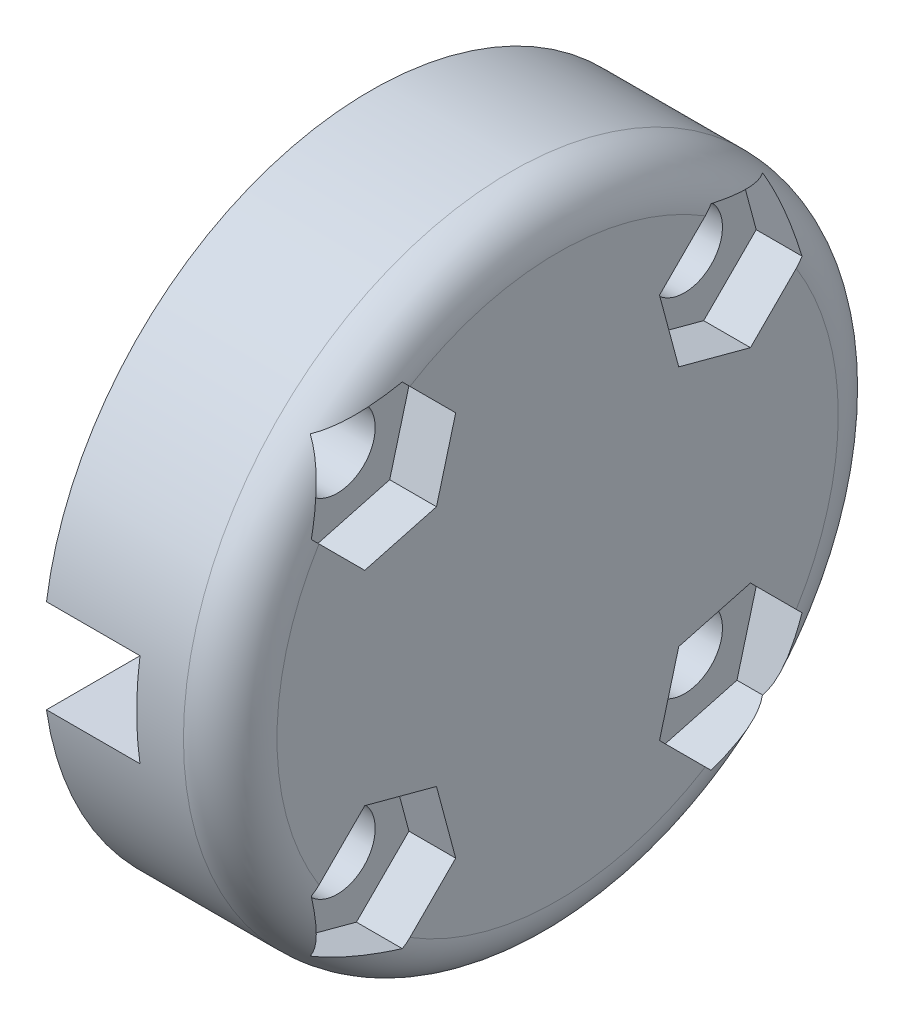
SolidWorks part; units mm, degrees
ref_plane "Front Plane" through (0, 0, 0) normal (0, 0, 1) x (1, 0, 0)
ref_plane "Top Plane" through (0, 0, 0) normal (0, 1, 0) x (1, 0, 0)
ref_plane "Right Plane" through (0, 0, 0) normal (1, 0, 0) x (0, 0, -1)
ref_plane "Plane1" through (-5, 0, 0) normal (1, 0, 0) x (0, 0, -1)
sketch "Sketch2" plane through (0, 0, 0) normal (1, 0, 0) x (0, 0, -1)
  line L1 (0, -14.5054) -> (0, 14.5054) construction
  line L2 (32.66, 0) -> (-15.2452, 0) construction
  line L3 (-10.918, -10.918) -> (10.918, 10.918) construction
  line L4 (12.2462, -12.2462) -> (-12.2462, 12.2462) construction
  circle A1 centre (0, 0) radius 2.625 construction
  circle A2 centre (0, 0) radius 14 construction
  circle A3 centre (0, 0) radius 10.5 construction
  circle A5 centre (0, 0) radius 24 construction
  point P17 (0, 0)
  point P18 (0, 0)
  point P19 (0, 0)
  dimension "D1" = 28
  dimension "D3" = 5.25
  dimension "D6" = 21
  dimension "D8" = 48
  dimension "D4" = 45
  dimension "D5" = 45
sketch "Sketch4" plane through (0, 0, 0) normal (1, 0, 0) x (0, 0, -1)
  line L0 (-10.918, -10.918) -> (10.918, 10.918) construction
  line L1 (12.2462, -12.2462) -> (-12.2462, 12.2462) construction
  circle A0 centre (0, 0) radius 14
  circle A1 centre (0, 0) radius 14 construction
  circle A2 centre (-7.4246, -7.4246) radius 1.625
  circle A3 centre (7.4246, -7.4246) radius 1.625
  circle A4 centre (7.4246, 7.4246) radius 1.625
  circle A5 centre (-7.4246, 7.4246) radius 1.625
  circle A6 centre (0, 0) radius 10.5 construction
  dimension "D1" = 3.25
  dimension "D2" = 3.25
  dimension "D3" = 3.25
  dimension "D4" = 3.25
extrude "Circular Foot" add sketch "Sketch4" along normal blind 8 separate body
fillet "Fillet1" radius 2 1 edges at (8, 0, -14)
sketch "Sketch7" plane through (8, 0, 0) normal (-1, 0, 0) x (0, 0, 1)
  line L0 (10.918, -10.918) -> (-10.918, 10.918) construction
  line L7 (-12.2462, -12.2462) -> (12.2462, 12.2462) construction
  line L8 (-5.1793, -5.1793) -> (-8.2465, -4.3574)
  line L9 (-8.2465, -4.3574) -> (-10.4918, -6.6028)
  line L10 (-10.4918, -6.6028) -> (-9.67, -9.67)
  line L11 (-9.67, -9.67) -> (-6.6028, -10.4918)
  line L12 (-6.6028, -10.4918) -> (-4.3574, -8.2465)
  line L13 (-4.3574, -8.2465) -> (-5.1793, -5.1793)
  line L14 (6.6028, -10.4918) -> (9.67, -9.67)
  line L15 (9.67, -9.67) -> (10.4918, -6.6028)
  line L16 (10.4918, -6.6028) -> (8.2465, -4.3574)
  line L17 (8.2465, -4.3574) -> (5.1793, -5.1793)
  line L18 (5.1793, -5.1793) -> (4.3574, -8.2465)
  line L19 (4.3574, -8.2465) -> (6.6028, -10.4918)
  line L20 (6.6028, 10.4918) -> (4.3574, 8.2465)
  line L21 (4.3574, 8.2465) -> (5.1793, 5.1793)
  line L22 (5.1793, 5.1793) -> (8.2465, 4.3574)
  line L23 (8.2465, 4.3574) -> (10.4918, 6.6028)
  line L24 (10.4918, 6.6028) -> (9.67, 9.67)
  line L25 (9.67, 9.67) -> (6.6028, 10.4918)
  line L27 (-4.3574, 8.2465) -> (-6.6028, 10.4918)
  line L28 (-6.6028, 10.4918) -> (-9.67, 9.67)
  line L29 (-9.67, 9.67) -> (-10.4918, 6.6028)
  line L30 (-10.4918, 6.6028) -> (-8.2465, 4.3574)
  line L31 (-8.2465, 4.3574) -> (-5.1793, 5.1793)
  line L32 (-5.1793, 5.1793) -> (-4.3574, 8.2465)
  circle A0 centre (-7.4246, 7.4246) radius 2.75 construction
  circle A3 centre (-7.4246, -7.4246) radius 2.75 construction
  circle A4 centre (7.4246, -7.4246) radius 2.75 construction
  circle A5 centre (7.4246, 7.4246) radius 2.75 construction
  circle A6 centre (0, 0) radius 10.5 construction
  dimension "D1" = 5.5
  dimension "D2" = 5.5
  dimension "D3" = 5.5
  dimension "D4" = 5.5
extrude "Cut-Extrude1" cut sketch "Sketch7" along normal blind 2
sketch "Sketch14" plane through (0, 0, 0) normal (0, 0, 1) x (1, 0, 0)
  line L0 (0, -24) -> (0, 24) construction
  line L1 (0, 2) -> (4, 2)
  line L2 (0, 2) -> (0, -2)
  line L3 (0, -2) -> (4, -2)
  line L4 (4, 2) -> (4, -2)
  point P6 (0, 0)
  dimension "D1" = 4
  dimension "D2" = 4
extrude "Cut-Extrude2" cut sketch "Sketch14" against normal through all both and the other way through all
sketch "Sketch16" plane through (0, 0, 0) normal (1, 0, 0) x (0, 0, -1)
  circle A0 centre (0, 0) radius 2.625
  circle A1 centre (0, 0) radius 2.625 construction
extrude "Cut-Extrude3" cut sketch "Sketch16" along normal blind 5
